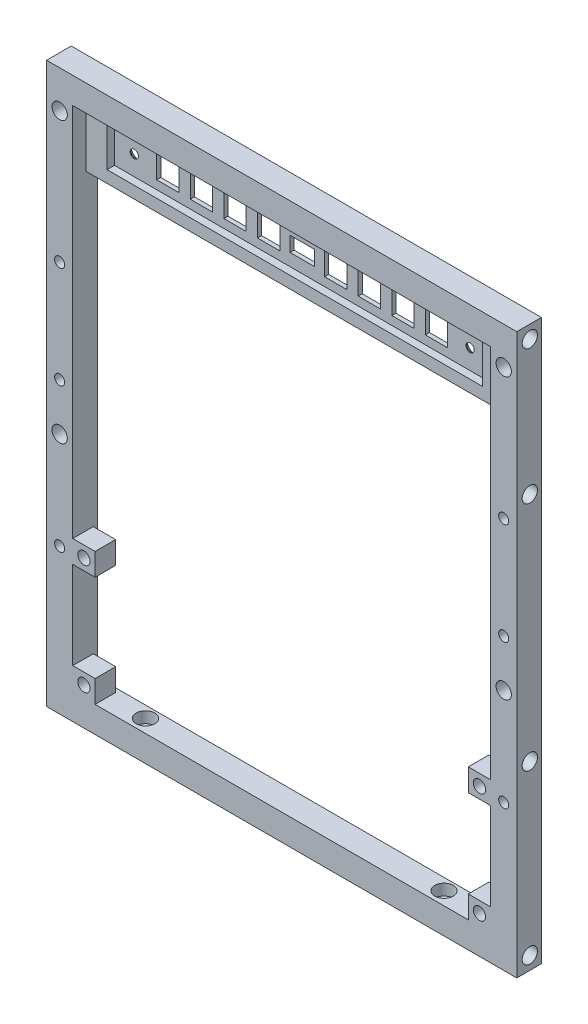
SolidWorks part; units mm, degrees
ref_plane "Front Plane" through (0, 0, 0) normal (0, 0, 1) x (1, 0, 0)
ref_plane "Top Plane" through (0, 0, 0) normal (0, 1, 0) x (1, 0, 0)
ref_plane "Right Plane" through (0, 0, 0) normal (1, 0, 0) x (0, 0, -1)
sketch "Sketch1" plane through (0, 0, 0) normal (0, 0, 1) x (1, 0, 0)
  line L1 (-63, -75) -> (63, -75)
  line L2 (-63, -75) -> (-63, 75)
  line L3 (-63, 75) -> (63, 75)
  line L4 (63, -75) -> (63, 75)
  line L5 (-63, -75) -> (63, 75) construction
  line L6 (-63, 75) -> (63, -75) construction
  line L7 (-56, -68) -> (56, -68)
  line L8 (-56, -68) -> (-56, 68)
  line L9 (-56, 68) -> (56, 68)
  line L10 (56, -68) -> (56, 68)
  line L11 (-56, -68) -> (56, 68) construction
  line L12 (-56, 68) -> (56, -68) construction
  point P0 (0, 0)
  point P6 (0, 0)
  dimension "D1" = 126
  dimension "D2" = 150
  dimension "D3" = 7
  dimension "D4" = 7
extrude "Boss-Extrude1" add sketch "Sketch1" along normal blind 7
sketch "Sketch2" plane through (-63, 0, 0) normal (-1, 0, 0) x (0, 0, 1)
  line L0 (3.5, 71.5) -> (3.5, -71.5) construction
  line L1 (7, 75) -> (0, 75) construction
  circle A0 centre (3.5, -71.5) radius 2.05
  circle A2 centre (3.5, 71.5) radius 2.05
  circle A3 centre (3.5, 35.5) radius 2.05
  circle A4 centre (3.5, -26.5) radius 2.05
  point P2 (3.5, 0)
  point P7 (3.5, 75)
  dimension "D2" = 4.1
  dimension "D3" = 36
  dimension "D4" = 45
  dimension "D1" = 3.5
extrude "Cut-Extrude1" cut sketch "Sketch2" against normal blind 6
mirror "Mirror1" about plane through (0, 0, 0) normal (1, 0, 0) of "Cut-Extrude1"
sketch "Sketch3" plane through (0, -68, 0) normal (0, 1, 0) x (1, 0, 0)
  line L0 (0, 0) -> (0, -7) construction
  line L1 (-56, 0) -> (56, 0) construction
  line L2 (-56, -7) -> (56, -7) construction
  line L3 (40, -3.5) -> (-40, -3.5) construction
  circle A0 centre (40, -3.5) radius 1.35
  circle A1 centre (-40, -3.5) radius 1.35
  point P9 (0, -3.5)
  dimension "D1" = 2.7
  dimension "D2" = 80
extrude "Cut-Extrude2" cut sketch "Sketch3" against normal through all
sketch "Sketch4" plane through (0, -68, 0) normal (0, 1, 0) x (1, 0, 0)
  circle A0 centre (40, -3.5) radius 2.5
  circle A1 centre (-40, -3.5) radius 2.5
  dimension "D1" = 5
extrude "Cut-Extrude3" cut sketch "Sketch4" against normal blind 3
sketch "Sketch5" plane through (0, 0, 0) normal (0, 0, -1) x (-1, 0, 0)
  line L0 (-59.5, -75) -> (-59.5, 75) construction
  line L1 (63, -75) -> (-63, -75) construction
  line L2 (-63, 75) -> (63, 75) construction
  line L3 (-56, 0) -> (-63, 0) construction
  line L4 (-56, -68) -> (-56, 68) construction
  line L5 (-63, -75) -> (-63, 75) construction
  line L6 (0, 75) -> (0, -75) construction
  line L7 (56, -68) -> (-56, -68) construction
  circle A0 centre (-59.5, 2.6) radius 1.35
  circle A1 centre (59.5, 2.6) radius 1.35
  circle A2 centre (-59.5, -36) radius 1.35
  circle A3 centre (59.5, -36) radius 1.35
  circle A4 centre (-59.5, 29.9) radius 1.35
  circle A5 centre (59.5, 29.9) radius 1.35
  point P12 (-59.5, 0)
  point P13 (-59.5, 0)
  dimension "D1" = 2.7
  dimension "D2" = 2.6
  dimension "D3" = 32
  dimension "D4" = 45.1
extrude "Cut-Extrude4" cut sketch "Sketch5" against normal through all
sketch "Sketch6" plane through (0, 0, 0) normal (0, 0, -1) x (-1, 0, 0)
  circle A0 centre (-59.5, 2.6) radius 2.5
  circle A1 centre (59.5, 2.6) radius 2.5
  circle A2 centre (-59.5, -36) radius 2.5
  circle A3 centre (59.5, -36) radius 2.5
  circle A4 centre (-59.5, 29.9) radius 2.5
  circle A5 centre (59.5, 29.9) radius 2.5
  dimension "D1" = 5
extrude "Cut-Extrude5" cut sketch "Sketch6" against normal blind 3
sketch "Sketch7" plane through (0, 0, 0) normal (0, 0, -1) x (-1, 0, 0)
  line L0 (-56, 68) -> (-63, 68) construction
  line L1 (-63, -75) -> (-63, 75) construction
  line L2 (-59.5, 65) -> (-59.5, -10) construction
  line L3 (-63, 75) -> (63, 75) construction
  circle A0 centre (-59.5, 65) radius 2.05
  circle A1 centre (-59.5, -10) radius 2.05
  point P8 (-59.5, 68)
  dimension "D1" = 4.1
  dimension "D2" = 10
  dimension "D3" = 75
extrude "Cut-Extrude6" cut sketch "Sketch7" against normal through all
mirror "Mirror2" about plane through (0, 0, 0) normal (1, 0, 0) of "Cut-Extrude6"
sketch "Sketch8" plane through (0, 0, 3) normal (0, 0, -1) x (-1, 0, 0)
  line L0 (-60.85, 32.0042) -> (-60.85, 27.7958)
  line L2 (-60.85, 0.4958) -> (-60.85, 4.7042)
  line L4 (-58.15, 0.4958) -> (-58.15, 4.7042)
  line L5 (-60.85, 0.4958) -> (-58.15, 4.7042) construction
  line L6 (-60.85, 4.7042) -> (-58.15, 0.4958) construction
  line L8 (-60.85, -38.1042) -> (-60.85, -33.8958)
  line L10 (-58.15, -38.1042) -> (-58.15, -33.8958)
  line L11 (-60.85, -38.1042) -> (-58.15, -33.8958) construction
  line L12 (-60.85, -33.8958) -> (-58.15, -38.1042) construction
  line L13 (-58.15, 32.0042) -> (-58.15, 27.7958)
  circle A0 centre (-59.5, 2.6) radius 2.5 construction
  circle A1 centre (-59.5, -36) radius 2.5 construction
  circle A2 centre (-59.5, -36) radius 2.5 construction
  arc A3 (-58.15, 4.7042) -> (-60.85, 4.7042) centre (-59.5, 2.6) ccw
  arc A4 (-58.15, -33.8958) -> (-60.85, -33.8958) centre (-59.5, -36) ccw
  circle A5 centre (-59.5, 2.6) radius 1.35 construction
  circle A6 centre (-59.5, -36) radius 1.35 construction
  arc A7 (-60.85, -38.1042) -> (-58.15, -38.1042) centre (-59.5, -36) ccw
  arc A8 (-60.85, 0.4958) -> (-58.15, 0.4958) centre (-59.5, 2.6) ccw
  circle A9 centre (-59.5, 29.9) radius 2.5 construction
  arc A10 (-60.85, 32.0042) -> (-58.15, 32.0042) centre (-59.5, 29.9) cw
  arc A11 (-58.15, 27.7958) -> (-60.85, 27.7958) centre (-59.5, 29.9) cw
  point P0 (-59.5, 2.6)
  point P8 (-59.5, -36)
extrude "Cut-Extrude7" cut sketch "Sketch8" against normal blind 0.2
sketch "Sketch9" plane through (0, 0, 3.2) normal (0, 0, -1) x (-1, 0, 0)
  line L0 (-58.15, 2.6) -> (-58.15, 4.7042) construction
  line L1 (-60.85, 1.25) -> (-58.15, 1.25)
  line L2 (-60.85, 1.25) -> (-60.85, 3.95)
  line L3 (-60.85, 3.95) -> (-58.15, 3.95)
  line L4 (-58.15, 1.25) -> (-58.15, 3.95)
  line L5 (-60.85, 1.25) -> (-58.15, 3.95) construction
  line L6 (-60.85, 3.95) -> (-58.15, 1.25) construction
  line L7 (-58.15, -38.1042) -> (-58.15, -33.8958) construction
  line L8 (-60.85, -37.35) -> (-58.15, -37.35)
  line L9 (-60.85, -37.35) -> (-60.85, -34.65)
  line L10 (-60.85, -34.65) -> (-58.15, -34.65)
  line L11 (-58.15, -37.35) -> (-58.15, -34.65)
  line L12 (-60.85, -37.35) -> (-58.15, -34.65) construction
  line L13 (-60.85, -34.65) -> (-58.15, -37.35) construction
  arc A0 (-58.15, 2.6) -> (-60.85, 2.6) centre (-59.5, 2.6) ccw construction
  point P0 (-59.5, 2.6)
  point P8 (-59.5, -36)
extrude "Cut-Extrude8" cut sketch "Sketch9" against normal blind 0.2
mirror "Mirror3" about plane through (0, 0, 0) normal (1, 0, 0) of "Cut-Extrude8", "Cut-Extrude7"
sketch "Sketch10" plane through (0, 0, 7) normal (0, 0, 1) x (1, 0, 0)
  line L0 (56, -68) -> (56, 68) construction
  line L1 (56, -68) -> (50, -68)
  line L2 (56, -68) -> (56, -62)
  line L3 (56, -62) -> (50, -62)
  line L4 (50, -68) -> (50, -62)
  line L5 (56, -38.5) -> (50, -38.5)
  line L6 (56, -38.5) -> (56, -32.5)
  line L7 (56, -32.5) -> (50, -32.5)
  line L8 (50, -38.5) -> (50, -32.5)
  line L9 (-56, -68) -> (56, -68) construction
  dimension "D1" = 6
  dimension "D2" = 35.5
extrude "Boss-Extrude2" add sketch "Sketch10" against normal offset from surface (5.5 mm away) 1.5 up to face at (-57.45, -10, 0)
sketch "Sketch11" plane through (0, 0, 1.5) normal (0, 0, -1) x (-1, 0, 0)
  line L0 (-56, -38.5) -> (-50, -32.5) construction
  line L2 (-56, -68) -> (-50, -62) construction
  circle A0 centre (-53, -35.5) radius 1.65
  circle A1 centre (-53, -65) radius 1.65
  dimension "D1" = 3.3
extrude "Cut-Extrude9" cut sketch "Sketch11" against normal through all
mirror "Mirror4" about plane through (0, 0, 0) normal (1, 0, 0) of "Cut-Extrude9", "Boss-Extrude2"
sketch "Sketch12" plane through (0, 0, 0) normal (0, 0, -1) x (-1, 0, 0)
  line L0 (56, 68) -> (56, -68) construction
  line L1 (-56, 68) -> (56, 68)
  line L2 (-56, 68) -> (-56, 51)
  line L3 (-56, 51) -> (56, 51)
  line L4 (56, 68) -> (56, 51)
  dimension "D1" = 17
extrude "Boss-Extrude3" add sketch "Sketch12" against normal blind 1.5
sketch "Sketch13" plane through (0, 0, 1.5) normal (0, 0, 1) x (1, 0, 0)
  line L0 (-56, 68) -> (56, 51) construction
  line L2 (-50.3, 54.2) -> (50.3, 54.2)
  line L3 (-50.3, 54.2) -> (-50.3, 64.8)
  line L4 (-50.3, 64.8) -> (50.3, 64.8)
  line L5 (50.3, 54.2) -> (50.3, 64.8)
  line L6 (-50.3, 54.2) -> (50.3, 64.8) construction
  line L7 (-50.3, 64.8) -> (50.3, 54.2) construction
  line L8 (-56, 51) -> (56, 51)
  line L9 (-56, 51) -> (-56, 68)
  line L10 (-56, 68) -> (56, 68)
  line L11 (56, 51) -> (56, 68)
  line L12 (-56, 51) -> (56, 68) construction
  line L13 (-56, 68) -> (56, 51) construction
  point P4 (0, 59.5)
  point P9 (0, 59.5)
  dimension "D1" = 100.6
  dimension "D2" = 10.6
extrude "Boss-Extrude4" add sketch "Sketch13" along normal blind 2
sketch "Sketch14" plane through (0, 0, 1.5) normal (0, 0, 1) x (1, 0, 0)
  line L0 (0, 64.8) -> (0, 54.2) construction
  line L1 (50.3, 64.8) -> (-50.3, 64.8) construction
  line L2 (-50.3, 54.2) -> (50.3, 54.2) construction
  line L3 (-50.3, 59.5) -> (50.3, 59.5) construction
  line L4 (50.3, 54.2) -> (50.3, 64.8) construction
  line L5 (-33, 62.5) -> (-39, 62.5)
  line L6 (-3.25, 57.5) -> (3.25, 57.5)
  line L7 (-3.25, 57.5) -> (-3.25, 61.5)
  line L8 (-3.25, 61.5) -> (3.25, 61.5)
  line L9 (3.25, 57.5) -> (3.25, 61.5)
  line L10 (-3.25, 57.5) -> (3.25, 61.5) construction
  line L11 (-3.25, 61.5) -> (3.25, 57.5) construction
  line L12 (6, 56.5) -> (12, 56.5)
  line L13 (6, 56.5) -> (6, 62.5)
  line L14 (6, 62.5) -> (12, 62.5)
  line L15 (12, 56.5) -> (12, 62.5)
  line L16 (6, 56.5) -> (12, 62.5) construction
  line L17 (6, 62.5) -> (12, 56.5) construction
  line L18 (15, 56.5) -> (21, 56.5)
  line L19 (15, 56.5) -> (15, 62.5)
  line L20 (15, 62.5) -> (21, 62.5)
  line L21 (21, 56.5) -> (21, 62.5)
  line L22 (15, 56.5) -> (21, 62.5) construction
  line L23 (15, 62.5) -> (21, 56.5) construction
  line L24 (24, 56.5) -> (30, 56.5)
  line L25 (24, 56.5) -> (24, 62.5)
  line L26 (24, 62.5) -> (30, 62.5)
  line L27 (30, 56.5) -> (30, 62.5)
  line L28 (24, 56.5) -> (30, 62.5) construction
  line L29 (24, 62.5) -> (30, 56.5) construction
  line L30 (33, 56.5) -> (39, 56.5)
  line L31 (33, 56.5) -> (33, 62.5)
  line L32 (33, 62.5) -> (39, 62.5)
  line L33 (39, 56.5) -> (39, 62.5)
  line L34 (33, 56.5) -> (39, 62.5) construction
  line L35 (33, 62.5) -> (39, 56.5) construction
  line L36 (-39, 56.5) -> (-39, 62.5)
  line L37 (-33, 56.5) -> (-39, 56.5)
  line L38 (-33, 56.5) -> (-33, 62.5)
  line L39 (-24, 62.5) -> (-30, 62.5)
  line L40 (-30, 56.5) -> (-30, 62.5)
  line L41 (-24, 56.5) -> (-30, 56.5)
  line L42 (-24, 56.5) -> (-24, 62.5)
  line L43 (-15, 62.5) -> (-21, 62.5)
  line L44 (-21, 56.5) -> (-21, 62.5)
  line L45 (-15, 56.5) -> (-21, 56.5)
  line L46 (-15, 56.5) -> (-15, 62.5)
  line L47 (-6, 62.5) -> (-12, 62.5)
  line L48 (-12, 56.5) -> (-12, 62.5)
  line L49 (-6, 56.5) -> (-12, 56.5)
  line L50 (-6, 56.5) -> (-6, 62.5)
  circle A0 centre (-45, 59.5) radius 1.3 construction
  circle A1 centre (45, 59.5) radius 1.3 construction
  point P6 (0, 59.5)
  point P11 (0, 59.5)
  point P16 (9, 59.5)
  point P21 (18, 59.5)
  point P26 (27, 59.5)
  point P31 (36, 59.5)
  dimension "D10" = 2.6
  dimension "D9" = 45
  dimension "D1" = 6.5
  dimension "D2" = 4
  dimension "D3" = 6
  dimension "D4" = 9
  dimension "D5" = 9
  dimension "D6" = 9
  dimension "D7" = 9
  dimension "D8" = 45
extrude "Cut-Extrude10" cut sketch "Sketch14" against normal through all
sketch "Sketch15" plane through (0, 0, 1.5) normal (0, 0, 1) x (1, 0, 0)
  circle A0 centre (-45, 59.5) radius 1
  circle A1 centre (45, 59.5) radius 1
  dimension "D1" = 2
extrude "Boss-Extrude5" add sketch "Sketch15" along normal up to surface (2 mm away) up to face at (0, 59.5, 3.5)
chamfer "Chamfer1" distance 0.4 angle 45 4 edges at (-56, -8.5, 0) (56, -8.5, 0) (0, -68, 0) (0, 51, 0)
chamfer "Chamfer2" distance 0.4 angle 45 4 edges at (0, 75, 0) (-63, 0, 0) (0, -75, 0) (63, 0, 0)
chamfer "Chamfer3" distance 0.4 angle 45 36 edges at (-36, 56.5, 0) (-39, 59.5, 0) (-36, 62.5, 0) (-33, 59.5, 0) (-27, 56.5, 0) (-30, 59.5, 0) (-27, 62.5, 0) (-24, 59.5, 0) (-18, 56.5, 0) (-21, 59.5, 0) (-18, 62.5, 0) (-15, 59.5, 0) (-9, 56.5, 0) (-12, 59.5, 0) (-9, 62.5, 0) (-6, 59.5, 0) (0, 57.5, 0) (-3.25, 59.5, 0) (0, 61.5, 0) (3.25, 59.5, 0) (9, 56.5, 0) (6, 59.5, 0) (9, 62.5, 0) (12, 59.5, 0) (18, 56.5, 0) (15, 59.5, 0) (18, 62.5, 0) (21, 59.5, 0) (36, 56.5, 0) (33, 59.5, 0) (36, 62.5, 0) (39, 59.5, 0) (27, 56.5, 0) (24, 59.5, 0) (27, 62.5, 0) (30, 59.5, 0)
sketch "Sketch16" plane through (0, 0, 7) normal (0, 0, 1) x (1, 0, 0)
  line L0 (-50, 51) -> (-50, 54.2)
  line L1 (-56, -32.5) -> (-50, -32.5)
  line L2 (-56, -32.5) -> (-56, -26.5)
  line L3 (-56, -26.5) -> (-50, -26.5)
  line L4 (-50, -32.5) -> (-50, -26.5)
  line L5 (56, -32.5) -> (50, -32.5)
  line L6 (56, -32.5) -> (56, -26.5)
  line L7 (56, -26.5) -> (50, -26.5)
  line L8 (50, -32.5) -> (50, -26.5)
  line L9 (56, 51) -> (50, 51) construction
  line L10 (56, 51) -> (56, 45)
  line L11 (56, 45) -> (50, 45)
  line L12 (50, 51) -> (50, 45)
  line L13 (-56, 51) -> (-50, 51) construction
  line L14 (-56, 51) -> (-56, 45)
  line L15 (-56, 45) -> (-50, 45)
  line L16 (-50, 51) -> (-50, 45)
  line L17 (-50.3, 54.2) -> (50.3, 54.2) construction
  line L18 (-50, 54.2) -> (-56, 54.2)
  line L19 (-56, 68) -> (-56, 51) construction
  line L20 (-56, 54.2) -> (-56, 51)
  line L21 (50, 51) -> (50, 54.2)
  line L22 (50, 54.2) -> (56, 54.2)
  line L23 (56, 51) -> (56, 68) construction
  line L24 (56, 54.2) -> (56, 51)
  dimension "D1" = 6
extrude "Boss-Extrude7" add sketch "Sketch16" against normal offset from surface (5.5 mm away) 1.5 up to face at (-36, 59.5, 0)
sketch "Sketch17" plane through (0, 0, 1.5) normal (0, 0, -1) x (-1, 0, 0)
  line L0 (-50, 45) -> (50, -26.5) construction
  line L1 (-50, -26.5) -> (-50, -38.5) construction
  line L2 (-53, -29.5) -> (53, -29.5) construction
  line L3 (-53, -29.5) -> (-53, 48) construction
  line L4 (-53, 48) -> (53, 48) construction
  line L5 (53, -29.5) -> (53, 48) construction
  line L6 (-53, -29.5) -> (53, 48) construction
  line L7 (-53, 48) -> (53, -29.5) construction
  line L8 (50, -26.5) -> (56, -26.5) construction
  circle A0 centre (-53, -29.5) radius 1.65
  circle A1 centre (53, -29.5) radius 1.65
  circle A2 centre (53, 48) radius 1.65
  circle A3 centre (-53, 48) radius 1.65
  point P4 (0, 9.25)
  dimension "D3" = 3.3
  dimension "D1" = 3
  dimension "D2" = 3
extrude "Cut-Extrude11" cut sketch "Sketch17" against normal through all
sketch "Sketch18" plane through (0, 0, 1.5) normal (0, 0, 1) x (1, 0, 0)
  circle A0 centre (-45, 59.5) radius 1.1
  circle A1 centre (45, 59.5) radius 1.1
  dimension "D1" = 2.2
extrude "Cut-Extrude12" cut sketch "Sketch18" against normal through all both and the other way through all
chamfer "Chamfer4" distance 1.3 angle 45 2 edges at (-43.9, 59.5, 0) (46.1, 59.5, 0)
sketch "Skizze1" plane through (0, 0, 7) normal (0, 0, 1) x (1, 0, 0)
  line L0 (-56, -38.5) -> (-56, -26.5) construction
  line L1 (56, 51) -> (-56, 51)
  line L2 (56, 51) -> (56, -32.5)
  line L3 (56, -32.5) -> (-56, -32.5)
  line L4 (-56, 51) -> (-56, -32.5)
extrude "Schnitt-Linear austragen1" cut sketch "Skizze1" against normal up to surface (5.5 mm away) up to face at (-54.65, 48, 1.5)
sketch "Skizze2" plane through (0, 0, 7) normal (0, 0, 1) x (1, 0, 0)
  line L1 (-56, 54.2) -> (56, 54.2)
  line L2 (-56, 54.2) -> (-56, 51)
  line L3 (-56, 51) -> (56, 51)
  line L4 (56, 54.2) -> (56, 51)
extrude "Schnitt-Linear austragen2" cut sketch "Skizze2" against normal up to surface (3.5 mm away) up to face at (0, 52.6, 3.5)
